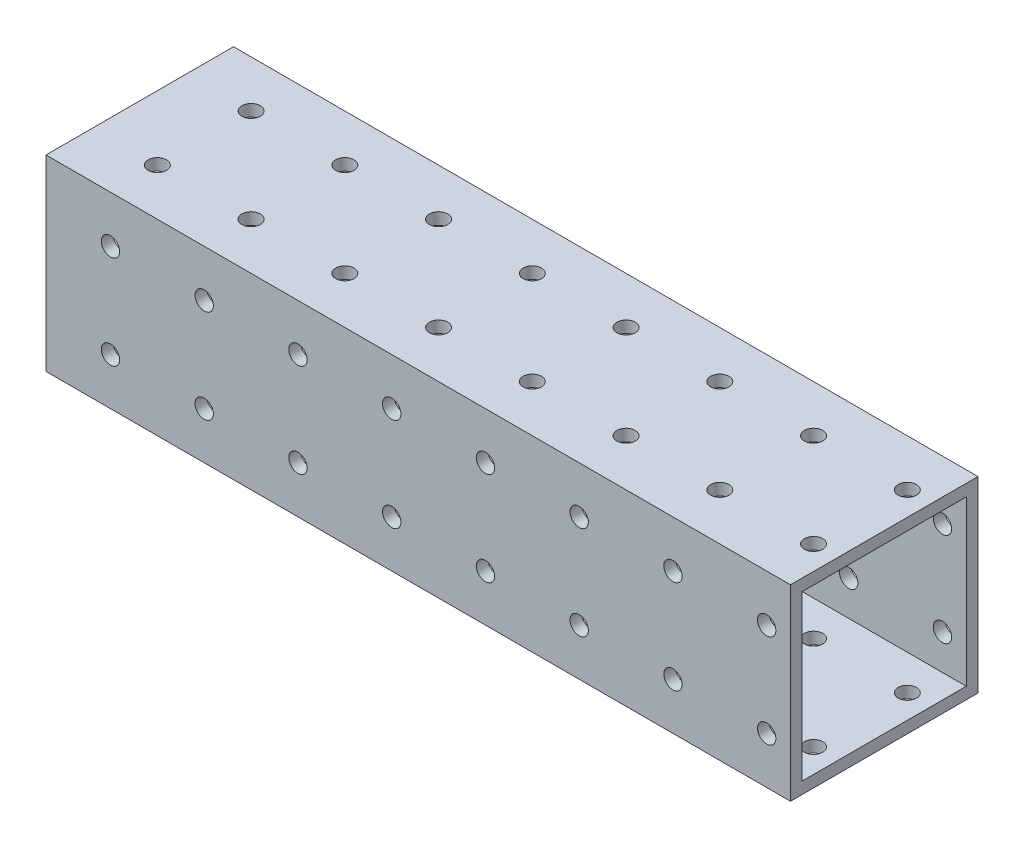
SolidWorks part; units mm, degrees
material "6061-T6 (SS)"
ref_plane "Front Plane" through (0, 0, 0) normal (0, 0, 1) x (1, 0, 0)
ref_plane "Top Plane" through (0, 0, 0) normal (0, 1, 0) x (1, 0, 0)
ref_plane "Right Plane" through (0, 0, 0) normal (1, 0, 0) x (0, 0, -1)
sketch "Sketch1" plane through (0, 0, 0) normal (1, 0, 0) x (0, 0, -1)
  line L1 (0, 0) -> (50.8, 0)
  line L2 (0, 0) -> (0, 50.8)
  line L3 (0, 50.8) -> (50.8, 50.8)
  line L4 (50.8, 0) -> (50.8, 50.8)
  dimension "D1" = 50.8
extrude "Boss-Extrude1" add sketch "Sketch1" along normal blind 201.7201
shell "Shell1" thickness 3.175 removed face at (0, 25.4, -25.4) removed face at (201.7201, 25.4, -25.4)
sketch "Sketch2" plane through (0, 0, -50.8) normal (0, 0, -1) x (-1, 0, 0)
  line L0 (-195.2625, 0) -> (-195.2625, 50.8) construction
  line L1 (-201.7201, 0) -> (0, 0) construction
  line L2 (-201.7201, 50.8) -> (0, 50.8) construction
  line L3 (-201.7201, 0) -> (-201.7201, 50.8) construction
  circle A22 centre (-195.2625, 38.1) radius 2.4892
  circle A23 centre (-195.2625, 12.7) radius 2.4892
  dimension "D2" = 4.9784
  dimension "D3" = 25.4
  dimension "D4" = 12.7
  dimension "D1" = 6.4576
extrude "Cut-Extrude3" cut sketch "Sketch2" against normal through all
sketch "Sketch3" plane through (0, 0, 0) normal (0, -1, 0) x (1, 0, 0)
  line L0 (195.2625, 0) -> (195.2625, -50.8) construction
  line L1 (201.7201, 0) -> (0, 0) construction
  line L2 (201.7201, -50.8) -> (0, -50.8) construction
  line L5 (201.7201, -50.8) -> (201.7201, 0) construction
  circle A2 centre (195.2625, -12.7) radius 2.4892
  circle A3 centre (195.2625, -38.1) radius 2.4892
  dimension "D1" = 4.9784
  dimension "D2" = 12.7
  dimension "D3" = 25.4
  dimension "D4" = 6.4576
extrude "Cut-Extrude2" cut sketch "Sketch3" against normal through all
pattern_linear "LPattern1" count 8 spacing 25.4 along (-1, 0, 0) of "Cut-Extrude2", "Cut-Extrude3"
